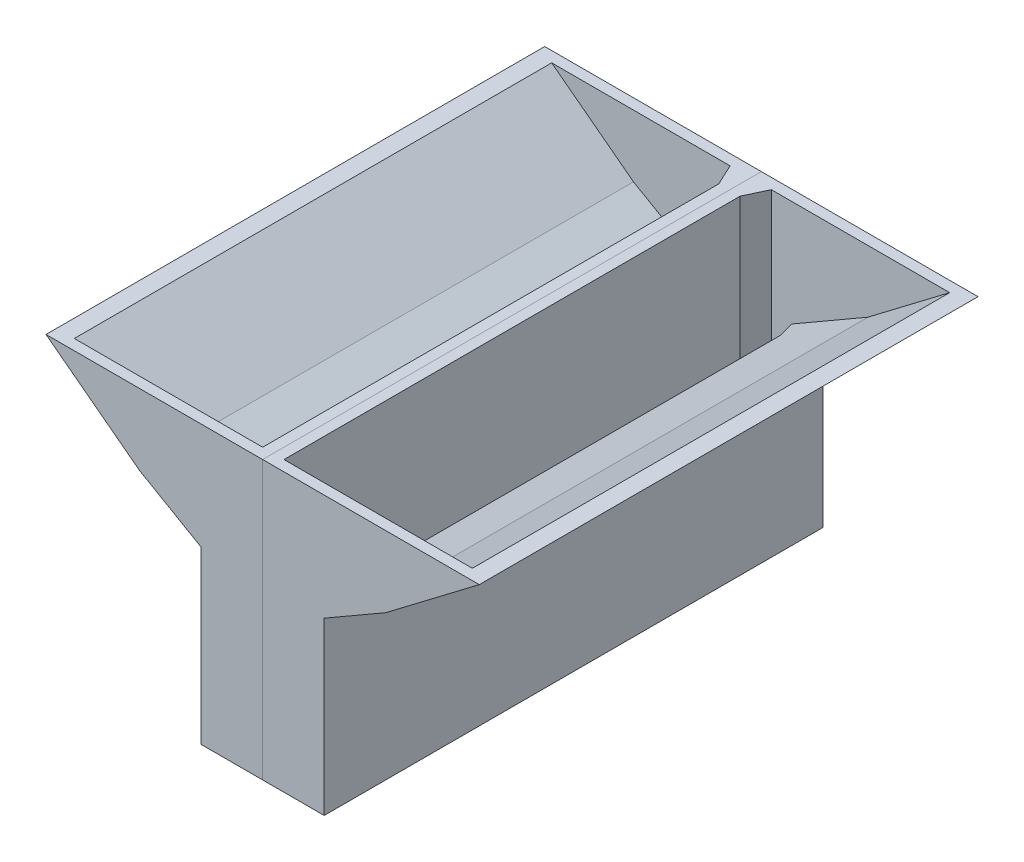
SolidWorks part; units mm, degrees
ref_plane "Front Plane" through (0, 0, 0) normal (0, 0, 1) x (1, 0, 0)
ref_plane "Top Plane" through (0, 0, 0) normal (0, 1, 0) x (1, 0, 0)
ref_plane "Right Plane" through (0, 0, 0) normal (1, 0, 0) x (0, 0, -1)
sketch "Sketch2" plane through (0, 0, 0) normal (0, 0, 1) x (1, 0, 0)
  line L0 (0, 0) -> (0, 700)
  line L2 (-346.4102, 500) -> (-173.2051, 400)
  line L3 (-173.2051, 400) -> (-173.2051, 0)
  line L4 (-173.2051, 0) -> (0, 0)
  line L5 (-346.4102, 500) -> (-609.6, 700)
  line L6 (-609.6, 700) -> (0, 700)
  dimension "D1" = 700
  dimension "D2" = 120
  dimension "D3" = 400
  dimension "D4" = 200
  dimension "D5" = 263.1898
  dimension "D6" = 609.6
extrude "Boss-Extrude1" add sketch "Sketch2" along normal mid plane 1403.35
shell "Shell1" thickness 30
sketch "Sketch3" plane through (0, 30, 0) normal (0, 1, 0) x (1, 0, 0)
  line L1 (-143.2051, 671.675) -> (-30, 671.675)
  line L2 (-143.2051, 671.675) -> (-143.2051, -671.675)
  line L3 (-143.2051, -671.675) -> (-30, -671.675)
  line L4 (-30, 671.675) -> (-30, -671.675)
extrude "Cut-Extrude1" cut sketch "Sketch3" against normal through all
sketch "Sketch4" plane through (0, 0, 0) normal (1, 0, 0) x (0, 0, -1)
  line L4 (-701.675, 0) -> (701.675, 0)
  line L5 (-701.675, 0) -> (-701.675, -80.8321)
  line L6 (-701.675, -80.8321) -> (701.675, -80.8321)
  line L7 (701.675, 0) -> (701.675, -80.8321)
  dimension "D1" = 1403.35
  dimension "D2" = 80.8321
extrude "Boss-Extrude2" add sketch "Sketch4" along direction (1, 0, 0) on the side against the normal up to vertex (173.2051 mm away)
ref_plane "Plane1" [suppressed] through (0, -80.8321, -701.675) normal (1, 0, 0) x (0, 0, -1)
sketch "Sketch8" plane through (-30, 0, 0) normal (-1, 0, 0) x (0, 0, 1)
  line L0 (701.675, 400) -> (701.675, -80.8321) construction
  line L2 (671.675, -50.8321) -> (-701.675, -50.8321)
  line L3 (671.675, -50.8321) -> (671.675, 99.1679)
  line L6 (701.675, -80.8321) -> (-701.675, -80.8321) construction
  line L8 (-701.675, 400) -> (-701.675, -80.8321) construction
  line L9 (-701.675, -50.8321) -> (671.675, 99.1679)
  dimension "D1" = 30
  dimension "D2" = 30
  dimension "D3" = 150
extrude "Boss-Extrude3" add sketch "Sketch8" along normal up to surface (113.2051 mm away)
sketch "Sketch10" plane through (0, 0, -701.675) normal (0, 0, -1) x (-1, 0, 0)
  line L0 (173.2051, -80.8321) -> (0, -80.8321) construction
  line L1 (56.6025, -80.8321) -> (116.6025, -80.8321)
  line L2 (56.6025, -80.8321) -> (56.6025, 319.1679)
  line L3 (56.6025, 319.1679) -> (116.6025, 319.1679)
  line L4 (116.6025, -80.8321) -> (116.6025, 319.1679)
  point P6 (86.6025, -80.8321)
  dimension "D1" = 400
  dimension "D2" = 60
extrude "Cut-Extrude5" cut sketch "Sketch10" against normal blind 30
sketch "Sketch11" plane through (-30, 0, 0) normal (-1, 0, 0) x (0, 0, 1)
  line L4 (-238.7344, 0) -> (-701.675, 0)
  line L5 (-701.675, 400) -> (-701.675, -80.8321) construction
  line L6 (-701.675, 0) -> (-701.675, -50.8321)
  line L7 (-701.675, -50.8321) -> (-238.7344, 0)
  dimension "D1" = 462.9406
extrude "Cut-Extrude6" cut sketch "Sketch11" along normal up to surface (113.2051 mm away)
sketch "Sketch12" plane through (0, 0, -701.675) normal (0, 0, -1) x (-1, 0, 0)
  line L1 (30, 0) -> (56.6025, 0)
  line L2 (30, 0) -> (30, -50.8321)
  line L3 (30, -50.8321) -> (56.6025, -50.8321)
  line L4 (56.6025, 0) -> (56.6025, -50.8321)
  line L5 (116.6025, 0) -> (143.2051, 0)
  line L6 (116.6025, 0) -> (116.6025, -50.8321)
  line L7 (116.6025, -50.8321) -> (143.2051, -50.8321)
  line L8 (143.2051, 0) -> (143.2051, -50.8321)
extrude "Boss-Extrude4" add sketch "Sketch12" against normal blind 30
chamfer "Chamfer3" distance 30 angle 60 1 edges at (-86.6025, -47.538, -671.675)
chamfer "Chamfer4" distance 60 angle 25 6 edges at (-43.3013, -47.538, -671.675) (-129.9038, -47.538, -671.675) (-30, 326.231, -671.675) (-143.2051, 184.8912, -671.675) (-56.6025, 135.8149, -671.675) (-116.6025, 135.8149, -671.675)
fillet "Fillet2" radius 15 2 edges at (-116.6025, -43.8533, -638.1174) (-56.6025, -43.8533, -638.1174)
mirror "Mirror2" about plane through (0, 0, 701.675) normal (-1, 0, 0) of bodies 114
scale "Scale2" [suppressed]
sketch "Sketch15" plane through (0, 0, 701.675) normal (0, 0, 1) x (1, 0, 0)
  line L2 (0, 700) -> (609.6, 700)
  line L3 (0, 700) -> (0, 629.7251)
  line L4 (0, 629.7251) -> (609.6, 629.7251)
  line L5 (609.6, 700) -> (609.6, 629.7251)
  dimension "D1" = 70.2749
extrude "Cut-Extrude9" [suppressed] cut sketch "Sketch15" against normal blind 701.675
